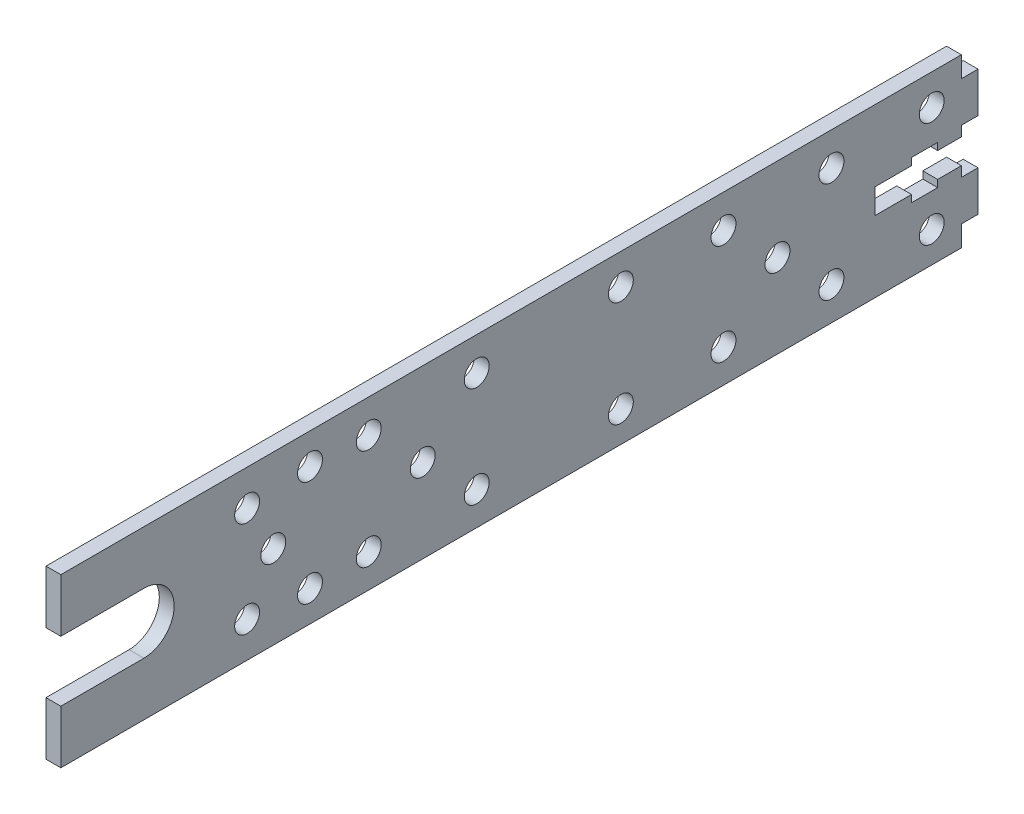
SolidWorks part; units mm, degrees
ref_plane "Front Plane" through (0, 0, 0) normal (0, 0, 1) x (1, 0, 0)
ref_plane "Top Plane" through (0, 0, 0) normal (0, 1, 0) x (1, 0, 0)
ref_plane "Right Plane" through (0, 0, 0) normal (1, 0, 0) x (0, 0, -1)
sketch "Sketch1" plane through (0, 0, 0) normal (1, 0, 0) x (0, 0, -1)
  line L0 (-98.171, 0) -> (98.171, 0) construction
  line L1 (-98.171, 17.907) -> (94.615, 17.907)
  line L2 (-98.171, 17.907) -> (-98.171, 6.477)
  line L3 (-98.171, -17.907) -> (94.615, -17.907)
  line L4 (98.171, 13.462) -> (98.171, 4.826)
  line L5 (94.615, 4.826) -> (94.615, 2.667)
  line L6 (94.615, -2.667) -> (94.615, -4.826)
  line L7 (94.615, 2.667) -> (89.535, 2.667)
  line L8 (94.615, 17.907) -> (94.615, 13.462)
  line L9 (94.615, -2.667) -> (89.535, -2.667)
  line L10 (76.073, 2.667) -> (76.073, -2.667)
  line L11 (86.741, 4.191) -> (86.741, -4.191) construction
  line L12 (-32.258, 10.795) -> (-9.144, 10.795) construction
  line L13 (83.947, 2.667) -> (76.073, 2.667)
  line L14 (89.535, 4.191) -> (83.947, 4.191)
  line L15 (89.535, 4.191) -> (89.535, 2.667)
  line L16 (89.535, -4.191) -> (83.947, -4.191)
  line L17 (83.947, 4.191) -> (83.947, 2.667)
  line L18 (66.802, 10.795) -> (43.688, 10.795) construction
  line L19 (66.802, -10.795) -> (43.688, -10.795) construction
  line L20 (83.947, -2.667) -> (76.073, -2.667)
  line L21 (89.535, -2.667) -> (89.535, -4.191)
  line L22 (83.947, -2.667) -> (83.947, -4.191)
  line L23 (98.171, -4.826) -> (98.171, -13.462)
  line L24 (98.171, 13.462) -> (94.615, 13.462)
  line L25 (98.171, 13.462) -> (98.171, 4.826)
  line L26 (98.171, 4.826) -> (94.615, 4.826)
  line L27 (-32.258, -10.795) -> (-9.144, -10.795) construction
  line L28 (98.171, 13.462) -> (94.615, 4.826) construction
  line L29 (98.171, 4.826) -> (94.615, 13.462) construction
  line L30 (-80.391, 6.477) -> (-98.171, 6.477)
  line L31 (98.171, -4.826) -> (94.615, -4.826)
  line L32 (-20.701, 10.795) -> (-20.701, -10.795) construction
  line L33 (98.171, -13.462) -> (94.615, -4.826) construction
  line L34 (98.171, -4.826) -> (94.615, -13.462) construction
  line L35 (98.171, -13.462) -> (94.615, -13.462)
  line L36 (-80.391, -6.477) -> (-98.171, -6.477)
  line L37 (-98.171, -6.477) -> (-98.171, -17.907)
  line L38 (94.615, -13.462) -> (94.615, -17.907)
  line L39 (55.245, 10.795) -> (55.245, -10.795) construction
  arc A0 (-80.391, -6.477) -> (-80.391, 6.477) centre (-80.391, 0) ccw
  circle A1 centre (-58.293, 10.287) radius 2.667
  circle A2 centre (-58.293, -10.287) radius 2.667
  circle A3 centre (-52.705, 0) radius 2.667
  circle A4 centre (-44.831, 11.303) radius 2.667
  circle A5 centre (21.717, 11.303) radius 2.667
  circle A6 centre (88.265, 11.303) radius 2.667
  circle A7 centre (88.265, -11.303) radius 2.667
  circle A8 centre (21.717, -11.303) radius 2.667
  circle A9 centre (-44.831, -11.303) radius 2.667
  circle A10 centre (-9.144, 10.795) radius 2.667
  circle A11 centre (-32.258, 10.795) radius 2.667
  circle A12 centre (66.802, 10.795) radius 2.667
  circle A13 centre (43.688, 10.795) radius 2.667
  circle A14 centre (43.688, -10.795) radius 2.667
  circle A15 centre (66.802, -10.795) radius 2.667
  circle A16 centre (-32.258, -10.795) radius 2.667
  circle A17 centre (-9.144, -10.795) radius 2.667
  circle A18 centre (-20.701, 0) radius 2.667
  circle A19 centre (55.245, 0) radius 2.667
  point P0 (0, 0)
  point P1 (86.741, 0)
  point P4 (0, 0)
  point P26 (96.393, 9.144)
  point P30 (96.393, -9.144)
  point P44 (76.073, 0)
  point P63 (55.245, 10.795)
  point P73 (-20.701, 10.795)
  dimension "D11" = 12.954
  dimension "D15" = 5.334
  dimension "D26" = 17.78
  dimension "D2" = 192.786
  dimension "D3" = 5.334
  dimension "D4" = 18.542
  dimension "D5" = 5.588
  dimension "D6" = 8.636
  dimension "D7" = 8.382
  dimension "D8" = 3.556
  dimension "D9" = 8.636
  dimension "D10" = 9.144
  dimension "D12" = 17.78
  dimension "D13" = 11.43
  dimension "D14" = 11.43
  dimension "D16" = 7.62
  dimension "D17" = 39.878
  dimension "D18" = 150.876
  dimension "D19" = 9.906
  dimension "D20" = 6.604
  dimension "D21" = 76.454
  dimension "D22" = 143.002
  dimension "D23" = 7.112
  dimension "D24" = 42.926
  dimension "D25" = 118.872
extrude "Boss-Extrude1" add sketch "Sketch1" along normal mid plane 3.175 contours A0 L36 L37 L3 L6 L9 L21 L16 L22 L20 L10 L13 L17 L14 L15 L7 L5 L26 L4 L24 L8 L1 L2 L30 A16 A14 A13 A12 A11 A10 A8 A2 A1 A3 A4 A5 region at (0, 0, -1.0471)
